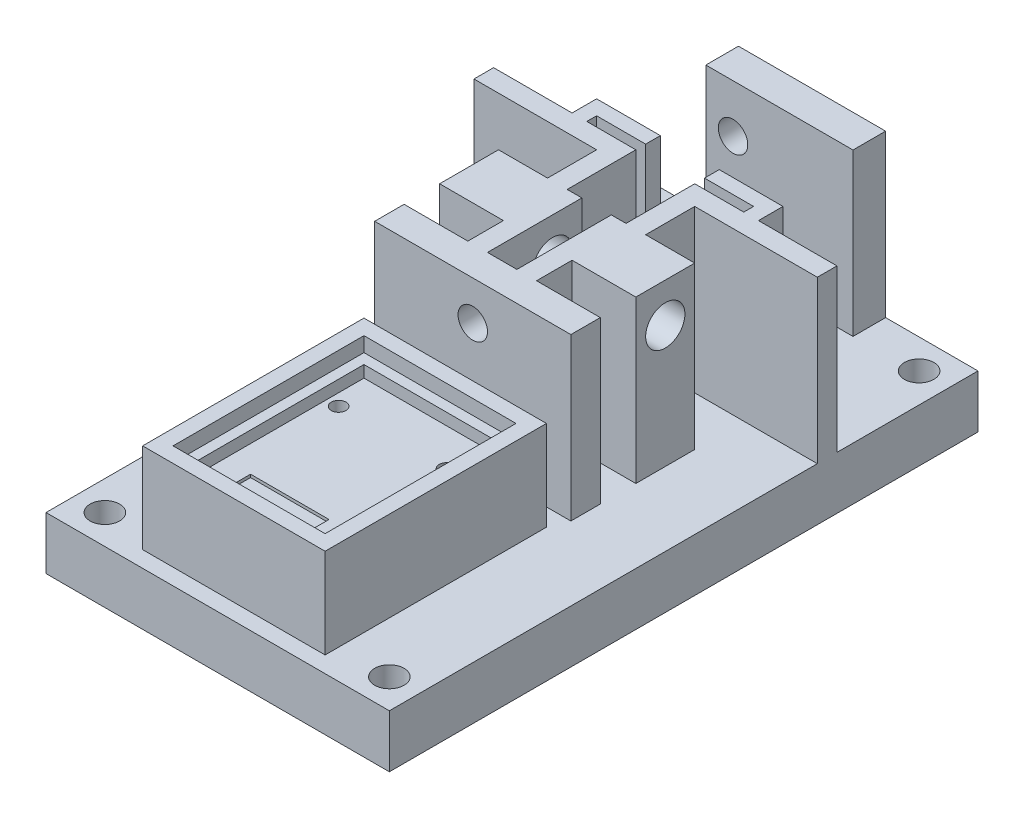
SolidWorks part; units mm, degrees
ref_plane "Front Plane" through (0, 0, 0) normal (0, 0, 1) x (1, 0, 0)
ref_plane "Top Plane" through (0, 0, 0) normal (0, 1, 0) x (1, 0, 0)
ref_plane "Right Plane" through (0, 0, 0) normal (1, 0, 0) x (0, 0, -1)
sketch "Sketch1" plane through (0, 0, 0) normal (0, 1, 0) x (1, 0, 0)
  line L5 (-17.5, 30) -> (17.5, 30)
  line L6 (-17.5, 30) -> (-17.5, -30)
  line L7 (-17.5, -30) -> (17.5, -30)
  line L8 (17.5, 30) -> (17.5, -30)
  point P5 (0, 30)
  point P7 (-17.5, 0)
  dimension "D1" = 60
  dimension "D2" = 35
extrude "FlatBase" add sketch "Sketch1" along normal blind 5.39
sketch "Sketch19" plane through (0, 5.39, 0) normal (0, 1, 0) x (1, 0, 0)
  line L0 (0, -14.5145) -> (0, 14.5145) construction
  line L1 (-14.5, 27) -> (14.5, 27) construction
  line L2 (-14.5, 27) -> (-14.5, -27) construction
  line L3 (-14.5, -27) -> (14.5, -27) construction
  line L4 (14.5, 27) -> (14.5, -27) construction
  line L5 (-14.5145, 0) -> (14.5145, 0) construction
  circle A0 centre (-14.5, 27) radius 1.5
  circle A1 centre (14.5, 27) radius 1.5
  circle A2 centre (14.5, -27) radius 1.5
  circle A3 centre (-14.5, -27) radius 1.5
  point P8 (0, 27)
  point P11 (14.5, 0)
  dimension "D1" = 3
  dimension "D2" = 54
  dimension "D3" = 29
extrude "FlatBaseHoles" cut sketch "Sketch19" against normal through all
sketch "Sketch2" plane through (0, 5.39, 0) normal (0, 1, 0) x (1, 0, 0)
  line L0 (0, -12.0175) -> (0, 12.0175) construction
  line L5 (-10, -1) -> (10, -1)
  line L6 (-10, -1) -> (-10, -4)
  line L7 (-10, -4) -> (10, -4)
  line L8 (10, -1) -> (10, -4)
  line L9 (-17.5, -30) -> (17.5, -30) construction
  point P7 (0, -4)
  dimension "D1" = 3
  dimension "D2" = 26
  dimension "D3" = 20
extrude "Filament-Laser-Interface" add sketch "Sketch2" along normal blind 16.46
sketch "Sketch4" plane through (0, 0, 1) normal (0, 0, -1) x (-1, 0, 0)
  line L1 (-10, 21.85) -> (10, 21.85) construction
  circle A0 centre (0, 17.85) radius 1.5
  dimension "D1" = 3
  dimension "D2" = 4
extrude "LaserHole" cut sketch "Sketch4" against normal up to surface (3 mm away) up to face at (0, 13.62, 4)
ref_axis "Laser Axis" through (0, 17.85, 4.3538) along (0, 0, -1)
ref_plane "Mid-Plane" through (0, 0, 0) normal (1, 0, 0) x (0, 0, -1)
sketch "Sketch8" plane through (0, 5.39, 0) normal (0, 1, 0) x (1, 0, 0)
  line L0 (-17.5, -30) -> (17.5, -30) construction
  line L1 (-7.6, -7.49) -> (7.6, -7.49) construction
  line L2 (-7.6, -7.49) -> (-7.6, -26.65) construction
  line L3 (-7.6, -26.65) -> (7.6, -26.65) construction
  line L4 (7.6, -7.49) -> (7.6, -26.65) construction
  line L6 (0, -7.49) -> (0, -5) construction
  line L7 (-10, -4) -> (10, -4) construction
  line L8 (-9.3, -5.79) -> (9.3, -5.79)
  line L9 (9.3, -5.79) -> (9.3, -28.35)
  line L10 (-9.3, -28.35) -> (9.3, -28.35)
  line L11 (-9.3, -5.79) -> (-9.3, -28.35)
  point P6 (0, -30)
  point P7 (0, -7.49)
  dimension "D1" = 15.2
  dimension "D2" = 19.16
  dimension "D3" = 2.49
  dimension "D4" = 1
  dimension "D5" = 1.7
extrude "Laser-Base" add sketch "Sketch8" along normal blind 7.66
sketch "Sketch9" plane through (0, 13.05, 0) normal (0, 1, 0) x (1, 0, 0)
  line L0 (-7.6, -26.65) -> (7.6, -26.65) construction
  line L1 (7.6, -7.49) -> (7.6, -26.65) construction
  line L2 (-7.6, -7.49) -> (-7.6, -26.65) construction
  line L3 (-7.6, -7.49) -> (7.6, -7.49) construction
  line L12 (-7.6, -26.65) -> (7.6, -26.65) construction
  line L13 (7.6, -7.49) -> (7.6, -26.65) construction
  line L14 (-7.6, -7.49) -> (-7.6, -26.65) construction
  line L15 (-7.6, -7.49) -> (7.6, -7.49) construction
  line L16 (-6.7, -8.39) -> (6.7, -8.39)
  line L17 (6.7, -8.39) -> (6.7, -25.75)
  line L18 (-6.7, -25.75) -> (6.7, -25.75)
  line L19 (-6.7, -8.39) -> (-6.7, -25.75)
  dimension "D2" = 0.9
extrude "LaserBoardMainCut" cut sketch "Sketch9" against normal blind 1.2
sketch "Sketch11" plane through (0, 13.05, 0) normal (0, 1, 0) x (1, 0, 0)
  line L0 (-7.6, -26.65) -> (7.6, -26.65) construction
  line L1 (-4, -26.65) -> (4, -26.65)
  line L2 (-4, -26.65) -> (-4, -22.65)
  line L3 (-4, -22.65) -> (4, -22.65)
  line L4 (4, -26.65) -> (4, -22.65)
  line L7 (0, -12.0175) -> (0, 12.0175) construction
  point P8 (0, -22.65)
  dimension "D1" = 4
  dimension "D2" = 8
extrude "LaserBoard-PinHples" cut sketch "Sketch11" against normal blind 1.5
sketch "Sketch13" plane through (0, 13.05, 0) normal (0, 1, 0) x (1, 0, 0)
  line L0 (-9.3, -28.35) -> (9.3, -28.35) construction
  line L1 (9.3, -28.35) -> (9.3, -5.79) construction
  line L2 (-9.3, -5.79) -> (-9.3, -28.35) construction
  line L3 (9.3, -5.79) -> (-9.3, -5.79) construction
  line L4 (-9.3, -28.35) -> (9.3, -28.35)
  line L5 (9.3, -28.35) -> (9.3, -5.79)
  line L6 (-9.3, -5.79) -> (-9.3, -28.35)
  line L7 (9.3, -5.79) -> (-9.3, -5.79)
  line L8 (7.75, -7.34) -> (-7.75, -7.34)
  line L9 (-7.75, -7.34) -> (-7.75, -26.8)
  line L10 (-7.75, -26.8) -> (7.75, -26.8)
  line L11 (7.75, -26.8) -> (7.75, -7.34)
  dimension "D1" = 1.55
extrude "LaserBoard-Skirting" add sketch "Sketch13" along normal blind 1.5
sketch "Sketch14" plane through (0, 11.85, 0) normal (0, 1, 0) x (1, 0, 0)
  line L0 (-5.5, -12.17) -> (5.5, -12.17) construction
  line L1 (-7.75, -7.34) -> (-7.75, -26.8) construction
  line L2 (7.75, -7.34) -> (-7.75, -7.34) construction
  circle A0 centre (5.5, -12.17) radius 0.75
  circle A1 centre (-5.5, -12.17) radius 0.75
  point P4 (0, -12.17)
  dimension "D2" = 1.5
  dimension "D1" = 11
  dimension "D3" = 2.25
  dimension "D4" = 4.83
extrude "LaserBoard-ScrewHoles" cut sketch "Sketch14" against normal through all
sketch "Sketch20" plane through (0, 5.39, 0) normal (0, 1, 0) x (1, 0, 0)
  line L0 (10, -1) -> (-10, -1) construction
  line L1 (-10, 2.6236) -> (10, 2.6236)
  line L2 (-10, 2.6236) -> (-10, 8.6236)
  line L3 (-10, 8.6236) -> (10, 8.6236)
  line L4 (10, 2.6236) -> (10, 8.6236)
  point P4 (0, 2.6236)
  dimension "D1" = 20
  dimension "D2" = 6
  dimension "D3" = 3.6236
extrude "Boss-Extrude1" add sketch "Sketch20" along normal up to surface (16.46 mm away) up to face at (0, 21.85, 2.5)
sketch "Sketch22" plane through (10, 0, 0) normal (1, 0, 0) x (0, 0, -1)
  line L0 (-4.3538, 17.85) -> (12.112, 17.85) construction
  line L1 (2.6236, 21.85) -> (8.6236, 21.85) construction
  circle A0 centre (5.6236, 17.85) radius 1.115
  point P7 (5.6236, 21.85)
  dimension "D1" = 2.23
extrude "Cut-Extrude1" cut sketch "Sketch22" against normal up to surface (20 mm away) up to face at (-10, 13.62, -5.6236)
sketch "Sketch23" plane through (0, 21.85, 0) normal (0, 1, 0) x (1, 0, 0)
  line L0 (10, 8.6236) -> (-10, 8.6236) construction
  line L1 (-1.5, 8.6236) -> (1.5, 8.6236)
  line L2 (-1.5, 8.6236) -> (-1.5, 2.6236)
  line L3 (-1.5, 2.6236) -> (1.5, 2.6236)
  line L4 (1.5, 8.6236) -> (1.5, 2.6236)
  line L5 (-10, 2.6236) -> (10, 2.6236) construction
  line L6 (0, -4.3538) -> (0, 12.112) construction
  point P8 (0, 8.6236)
  dimension "D1" = 3
extrude "Cut-Extrude2" cut sketch "Sketch23" against normal blind 10
sketch "Sketch24" plane through (10, 0, 0) normal (1, 0, 0) x (0, 0, -1)
  circle A0 centre (5.6236, 17.85) radius 2
  dimension "D1" = 4
extrude "Cut-Extrude3" cut sketch "Sketch24" against normal blind 4
sketch "Sketch25" plane through (-1.5, 0, 0) normal (1, 0, 0) x (0, 0, -1)
  circle A0 centre (5.6236, 17.85) radius 2
  circle A1 centre (5.6236, 17.85) radius 2 construction
extrude "Cut-Extrude4" cut sketch "Sketch25" against normal blind 4
sketch "Sketch26" plane through (0, 5.39, 0) normal (0, 1, 0) x (1, 0, 0)
  line L0 (10, -1) -> (-10, -1) construction
  line L1 (1.5, 2.6236) -> (3.5, 2.6236)
  line L2 (1.5, 2.6236) -> (1.5, -1)
  line L3 (1.5, -1) -> (3.5, -1)
  line L4 (3.5, 2.6236) -> (3.5, -1)
  line L5 (-10, 2.6236) -> (10, 2.6236) construction
  line L6 (-1.5, 2.6236) -> (-3.5, 2.6236)
  line L7 (-1.5, 2.6236) -> (-1.5, -1)
  line L8 (-1.5, -1) -> (-3.5, -1)
  line L9 (-3.5, 2.6236) -> (-3.5, -1)
  line L10 (-1.5, 8.6236) -> (-1.5, 2.6236) construction
  dimension "D1" = 2
extrude "Boss-Extrude2" add sketch "Sketch26" along normal up to surface (16.46 mm away) up to face at (5.75, 21.85, -5.6236)
sketch "Sketch27" plane through (0, 5.39, 0) normal (0, 1, 0) x (1, 0, 0)
  line L0 (17.5, 30) -> (-17.5, 30) construction
  line L1 (-6.915, 26.6736) -> (8.085, 26.6736)
  line L2 (-6.915, 26.6736) -> (-6.915, 30)
  line L3 (-6.915, 30) -> (8.085, 30)
  line L4 (8.085, 26.6736) -> (8.085, 30)
  dimension "D1" = 15
extrude "Boss-Extrude3" add sketch "Sketch27" along normal up to surface (16.46 mm away) up to face at (0, 21.85, -1.9368)
sketch "Sketch28" plane through (0, 0, -26.6736) normal (0, 0, 1) x (1, 0, 0)
  circle A0 centre (-4.145, 8.195) radius 1.5 construction
  circle A1 centre (-4.145, 16.945) radius 1.5 construction
  circle A2 centre (-4.145, 8.195) radius 1.5
  circle A3 centre (-4.145, 16.945) radius 1.5
extrude "Cut-Extrude5" cut sketch "Sketch28" against normal up to surface (3.3264 mm away) up to face at (0.2925, 8.1575, -30)
sketch "Sketch29" plane through (0, 5.39, 0) normal (0, 1, 0) x (1, 0, 0)
  line L0 (-17.5, 30) -> (-17.5, -30) construction
  line L5 (17.5, -30) -> (17.5, 30) construction
  line L6 (0, -12.0175) -> (0, 12.0175) construction
  line L7 (-17.5, 15.6236) -> (-9.5, 15.6236)
  line L8 (-17.5, 15.6236) -> (-17.5, 13.6236)
  line L9 (-17.5, 13.6236) -> (-5, 13.6236)
  line L10 (17.5, 15.6236) -> (17.5, 13.6236)
  line L12 (-9.5, 15.6236) -> (-9.5, 18.1236)
  line L13 (-9.5, 18.1236) -> (-3, 18.1236)
  line L14 (-3, 18.1236) -> (-3, 16.6236)
  line L15 (-3, 16.6236) -> (-8, 16.6236)
  line L16 (-8, 16.6236) -> (-8, 15.6236)
  line L17 (-8, 15.6236) -> (-3, 15.6236)
  line L18 (-9.5, 15.6236) -> (-8, 15.6236) construction
  line L19 (-1.5, 8.6236) -> (-10, 8.6236) construction
  line L20 (0, -15.7522) -> (0, 65.5118) construction
  line L21 (8, 16.6236) -> (8, 15.6236)
  line L22 (3, 18.1236) -> (3, 16.6236)
  line L23 (3, 16.6236) -> (8, 16.6236)
  line L24 (9.5, 15.6236) -> (9.5, 18.1236)
  line L25 (9.5, 18.1236) -> (3, 18.1236)
  line L26 (9.5, 15.6236) -> (17.5, 15.6236)
  line L27 (-3, 15.6236) -> (-3, 13.6236)
  line L28 (3, 15.6236) -> (3, 13.6236)
  line L29 (3, 15.6236) -> (8, 15.6236)
  line L30 (5, 13.6236) -> (17.5, 13.6236)
  line L31 (-3, 13.6236) -> (-3, 8.6236)
  line L32 (-5, 13.6236) -> (-5, 8.6236)
  line L33 (10, 8.6236) -> (-10, 8.6236) construction
  line L34 (3, 13.6236) -> (3, 8.6236)
  line L35 (5, 13.6236) -> (5, 8.6236)
  line L36 (3, 8.6236) -> (5, 8.6236)
  line L37 (-5, 8.6236) -> (-3, 8.6236)
  dimension "D1" = 2
  dimension "D2" = 1.5
  dimension "D3" = 1
  dimension "D4" = 5
  dimension "D5" = 5
  dimension "D6" = 3
  dimension "D7" = 2
extrude "Boss-Extrude4" add sketch "Sketch29" along normal up to surface (16.46 mm away) up to face at (0, 21.85, -1.9368)
